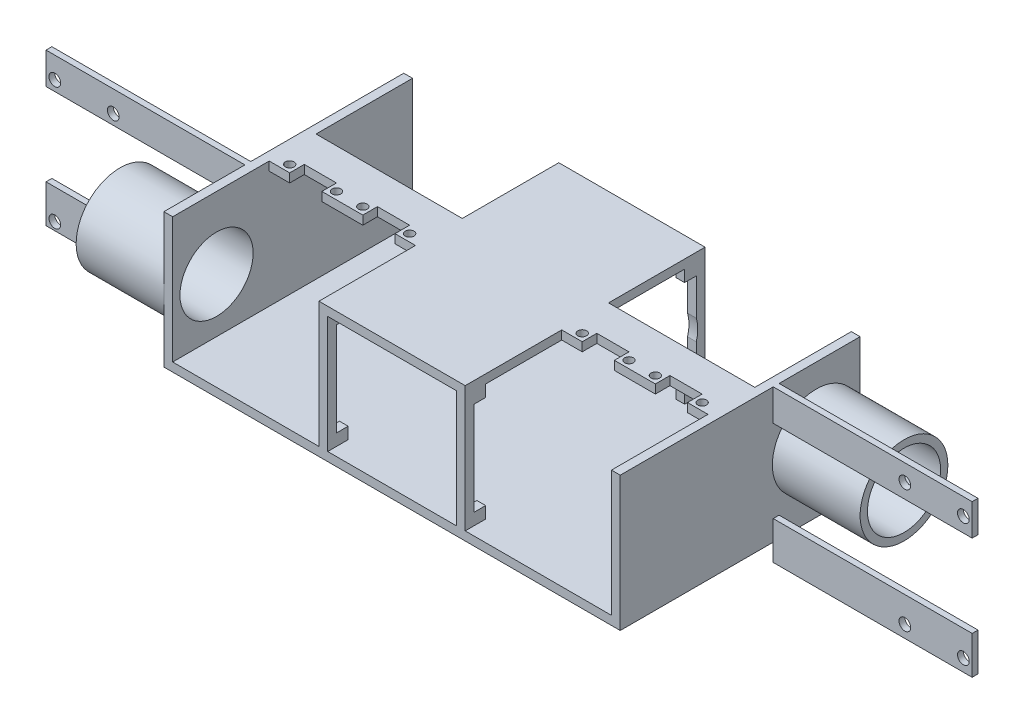
SolidWorks part; units mm, degrees
material "ABS PC"
ref_plane "Front Plane" through (0, 0, 0) normal (0, 0, 1) x (1, 0, 0)
ref_plane "Top Plane" through (0, 0, 0) normal (0, 1, 0) x (1, 0, 0)
ref_plane "Right Plane" through (0, 0, 0) normal (1, 0, 0) x (0, 0, -1)
sketch "Sketch1" plane through (0, 0, 0) normal (0, 0, 1) x (1, 0, 0)
  line L1 (-25, -23) -> (25, -23)
  line L2 (-25, -23) -> (-25, 23)
  line L3 (-25, 23) -> (25, 23)
  line L4 (25, -23) -> (25, 23)
  line L5 (-25, -23) -> (25, 23) construction
  line L6 (-25, 23) -> (25, -23) construction
  point P0 (0, 0)
  dimension "D1" = 50
  dimension "D2" = 46
extrude "Boss-Extrude1" add sketch "Sketch1" along normal mid plane 82
sketch "Sketch2" plane through (0, 0, 41) normal (0, 0, 1) x (1, 0, 0)
  line L0 (25, 23) -> (-25, 23) construction
  line L1 (-22, 20) -> (22, 20)
  line L2 (-22, 20) -> (-22, -20)
  line L3 (-22, -20) -> (22, -20)
  line L4 (22, 20) -> (22, -20)
  line L5 (-22, 20) -> (22, -20) construction
  line L6 (-22, -20) -> (22, 20) construction
  line L7 (-25, 23) -> (-25, -23) construction
  point P0 (0, 0)
  dimension "D1" = 3
  dimension "D2" = 3
extrude "Cut-Extrude1" cut sketch "Sketch2" against normal up to next
sketch "Sketch3" plane through (-25, 0, 0) normal (-1, 0, 0) x (0, 0, 1)
  line L0 (-34, 16) -> (-34, 20)
  line L1 (-34, 20) -> (34, 20)
  line L2 (34, 20) -> (34, 16)
  line L3 (34, 16) -> (38, 16)
  line L4 (38, 16) -> (38, -16)
  line L5 (38, -16) -> (34, -16)
  line L6 (34, -16) -> (34, -20)
  line L7 (34, -20) -> (-34, -20)
  line L8 (-34, -20) -> (-34, -16)
  line L9 (-34, -16) -> (-38, -16)
  line L10 (-38, -16) -> (-38, 16)
  line L11 (-38, 16) -> (-34, 16)
  line L12 (41, 23) -> (-41, 23) construction
  line L13 (-41, 23) -> (-41, -23) construction
  line L14 (41, 23) -> (41, -23) construction
  line L15 (41, -23) -> (-41, -23) construction
  dimension "D1" = 3
  dimension "D2" = 3
  dimension "D3" = 3
  dimension "D4" = 3
  dimension "D5" = 7
  dimension "D6" = 7
  dimension "D7" = 7
  dimension "D8" = 7
  dimension "D9" = 7
  dimension "D10" = 7
  dimension "D11" = 7
  dimension "D12" = 7
extrude "Cut-Extrude2" cut sketch "Sketch3" against normal through all both and the other way through all
sketch "Sketch4" plane through (25, 0, 0) normal (1, 0, 0) x (0, 0, -1)
  line L0 (41, -23) -> (41, 23) construction
  line L1 (-41, -23) -> (41, -23)
  line L2 (-41, -23) -> (-41, -20)
  line L3 (-41, -20) -> (41, -20)
  line L4 (41, -23) -> (41, -20)
  dimension "D1" = 3
extrude "Boss-Extrude2" add sketch "Sketch4" along normal blind 50
sketch "Sketch7" plane through (25, 0, 0) normal (1, 0, 0) x (0, 0, -1)
  line L0 (-41, 23) -> (41, 23) construction
  line L1 (-8, 23) -> (8, 23)
  line L2 (-8, 23) -> (-8, 20)
  line L3 (-8, 20) -> (8, 20)
  line L4 (8, 23) -> (8, 20)
  line L5 (-34, 20) -> (34, 20) construction
  line L7 (-41, -20) -> (-41, 23) construction
  dimension "D1" = 16
  dimension "D2" = 33
extrude "Boss-Extrude4" add sketch "Sketch7" along normal blind 50
sketch "Sketch8" plane through (75, 0, 0) normal (1, 0, 0) x (0, 0, -1)
  line L1 (-41, -23) -> (41, -23)
  line L2 (-41, -23) -> (-41, 23)
  line L3 (-41, 23) -> (41, 23)
  line L4 (41, -23) -> (41, 23)
  dimension "D1" = 46
  dimension "D2" = 82
extrude "Boss-Extrude5" add sketch "Sketch8" along normal blind 3
sketch "Sketch9" plane through (0, 23, 0) normal (0, 1, 0) x (1, 0, 0)
  line L0 (68, -8) -> (68, -3)
  line L1 (75, -8) -> (25, -8) construction
  line L2 (68, -3) -> (57, -3)
  line L3 (57, -3) -> (57, -8)
  line L4 (75, -8) -> (75, -41) construction
  dimension "D1" = 7
  dimension "D2" = 18
  dimension "D3" = 5
extrude "Cut-Extrude4" cut sketch "Sketch9" against normal blind 3 and the other way through all
sketch "Sketch10" plane through (0, 23, 0) normal (0, 1, 0) x (1, 0, 0)
  line L0 (32, -8) -> (32, -3)
  line L1 (57, -8) -> (25, -8) construction
  line L2 (32, -3) -> (43, -3)
  line L3 (43, -3) -> (43, -8)
  line L4 (43, -8) -> (32, -8)
  line L5 (25, -41) -> (25, -8) construction
  dimension "D1" = 5
  dimension "D2" = 11
  dimension "D3" = 7
extrude "Cut-Extrude5" cut sketch "Sketch10" against normal up to next
sketch "Sketch11" plane through (0, 23, 0) normal (0, 1, 0) x (1, 0, 0)
  line L0 (75, -8) -> (68, -8) construction
  line L1 (68, -3) -> (68, -8) construction
  line L2 (57, -8) -> (57, -3) construction
  line L3 (57, -8) -> (43, -8) construction
  line L4 (43, -8) -> (43, -3) construction
  line L5 (32, -8) -> (25, -8) construction
  line L6 (32, -3) -> (32, -8) construction
  circle A0 centre (29.5, -5.5) radius 1.5
  circle A1 centre (45.5, -5.5) radius 1.5
  circle A2 centre (54.5, -5.5) radius 1.5
  circle A3 centre (70.5, -5.5) radius 1.5
  dimension "D1" = 3
  dimension "D2" = 3
  dimension "D3" = 3
  dimension "D4" = 3
  dimension "D5" = 2.5
  dimension "D6" = 2.5
  dimension "D7" = 2.5
  dimension "D8" = 2.5
  dimension "D9" = 2.5
  dimension "D10" = 2.5
  dimension "D11" = 2.5
  dimension "D12" = 2.5
extrude "Cut-Extrude6" cut sketch "Sketch11" against normal up to next
sketch "Sketch12" plane through (78, 0, 0) normal (1, 0, 0) x (0, 0, -1)
  line L0 (41, -23) -> (41, 23) construction
  circle A0 centre (26, 0) radius 15
  dimension "D1" = 30
  dimension "D2" = 15
extrude "Boss-Extrude6" add sketch "Sketch12" along normal blind 30
sketch "Sketch13" plane through (108, 0, 0) normal (1, 0, 0) x (0, 0, -1)
  line L0 (41, -23) -> (41, 0) construction
  circle A0 centre (26, 0) radius 12.5
  dimension "D1" = 25
  dimension "D2" = 15
extrude "Cut-Extrude7" cut sketch "Sketch13" against normal through all
sketch "Sketch14" plane through (78, 0, 0) normal (1, 0, 0) x (0, 0, -1)
  line L0 (41, 23) -> (-41, 23) construction
  line L1 (11.3, 23) -> (13.3, 23)
  line L2 (11.3, 23) -> (11.3, 12.2)
  line L3 (11.3, 12.2) -> (13.3, 12.2)
  line L4 (13.3, 23) -> (13.3, 12.2)
  line L11 (-41, 23) -> (-41, -23) construction
  line L12 (11.3, -16) -> (13.3, -16)
  line L13 (11.3, -16) -> (11.3, -29)
  line L14 (11.3, -29) -> (13.3, -29)
  line L15 (13.3, -16) -> (13.3, -29)
  line L16 (-41, -23) -> (41, -23) construction
  dimension "D1" = 10.8
  dimension "D2" = 52.3
  dimension "D3" = 2
  dimension "D4" = 13
  dimension "D5" = 54.3
  dimension "D6" = 2
  dimension "D7" = 7
extrude "Boss-Extrude7" add sketch "Sketch14" along normal blind 68
sketch "Sketch15" plane through (0, 0, -13.3) normal (0, 0, -1) x (-1, 0, 0)
  line L1 (-78, 23) -> (-78, 12.2) construction
  line L2 (-78, -16) -> (-78, -23) construction
  line L4 (-146, 12.2) -> (-78, 12.2) construction
  circle A0 centre (-143, -24.8) radius 2
  circle A1 centre (-123, -24.8) radius 2
  circle A2 centre (-123, 17.2) radius 2
  circle A3 centre (-143, 17.2) radius 2
  dimension "D1" = 4
  dimension "D2" = 4
  dimension "D3" = 4
  dimension "D4" = 4
  dimension "D5" = 45
  dimension "D6" = 45
  dimension "D7" = 20
  dimension "D8" = 20
  dimension "D9" = 5
  dimension "D10" = 42
  dimension "D11" = 5
  dimension "D12" = 42
mirror "Mirror1" about plane through (0, 0, 0) normal (1, 0, 0) of "Cut-Extrude6", "Cut-Extrude5", "Boss-Extrude5", "Boss-Extrude2", "Boss-Extrude4", "Cut-Extrude4"
sketch "Sketch16" plane through (-78, 0, 0) normal (-1, 0, 0) x (0, 0, 1)
  line L0 (41, 23) -> (41, -23) construction
  circle A0 centre (26, -1.5051) radius 15
  dimension "D1" = 30
  dimension "D2" = 15
extrude "Boss-Extrude8" add sketch "Sketch16" along normal blind 30
sketch "Sketch17" plane through (-108, 0, 0) normal (-1, 0, 0) x (0, 0, 1)
  circle A0 centre (26, -1.5051) radius 12.5
  dimension "D1" = 25
extrude "Cut-Extrude9" cut sketch "Sketch17" against normal up to next
sketch "Sketch18" plane through (-78, 0, 0) normal (-1, 0, 0) x (0, 0, 1)
  line L1 (11.3, 12.2) -> (13.3, 12.2)
  line L2 (11.3, 12.2) -> (11.3, 23)
  line L3 (11.3, 23) -> (13.3, 23)
  line L4 (13.3, 12.2) -> (13.3, 23)
  line L5 (-41, -23) -> (-41, 23) construction
  line L6 (-41, 23) -> (41, 23) construction
  dimension "D1" = 10.8
  dimension "D2" = 54.3
  dimension "D3" = 2
  dimension "D4" = 0
extrude "Boss-Extrude9" add sketch "Sketch18" along normal blind 68
sketch "Sketch19" plane through (-78, 0, 0) normal (-1, 0, 0) x (0, 0, 1)
  line L0 (41, -23) -> (-41, -23) construction
  line L1 (11.3, -29) -> (13.3, -29)
  line L2 (11.3, -29) -> (11.3, -16)
  line L3 (11.3, -16) -> (13.3, -16)
  line L4 (13.3, -29) -> (13.3, -16)
  line L5 (-41, -23) -> (-41, 23) construction
  dimension "D1" = 13
  dimension "D2" = 7
  dimension "D3" = 54.3
  dimension "D4" = 2
extrude "Boss-Extrude10" add sketch "Sketch19" along normal blind 68
sketch "Sketch20" plane through (0, 0, 13.3) normal (0, 0, 1) x (1, 0, 0)
  line L0 (-78, 12.2) -> (-78, 23) construction
  line L1 (-146, 12.2) -> (-78, 12.2) construction
  line L2 (-146, -29) -> (-78, -29) construction
  circle A0 centre (-123, 15.6949) radius 2
  circle A1 centre (-143, 15.6949) radius 2
  circle A2 centre (-123, -26.3051) radius 2
  circle A3 centre (-143, -26.3051) radius 2
  dimension "D5" = 4
  dimension "D6" = 4
  dimension "D7" = 4
  dimension "D8" = 4
  dimension "D1" = 20
  dimension "D2" = 20
  dimension "D3" = 42
  dimension "D4" = 42
  dimension "D9" = 45
  dimension "D10" = 3.4949
  dimension "D11" = 2.6949
  dimension "D12" = 3.4949
extrude "Cut-Extrude10" cut sketch "Sketch15" against normal up to next
extrude "Cut-Extrude11" cut sketch "Sketch20" against normal up to next
